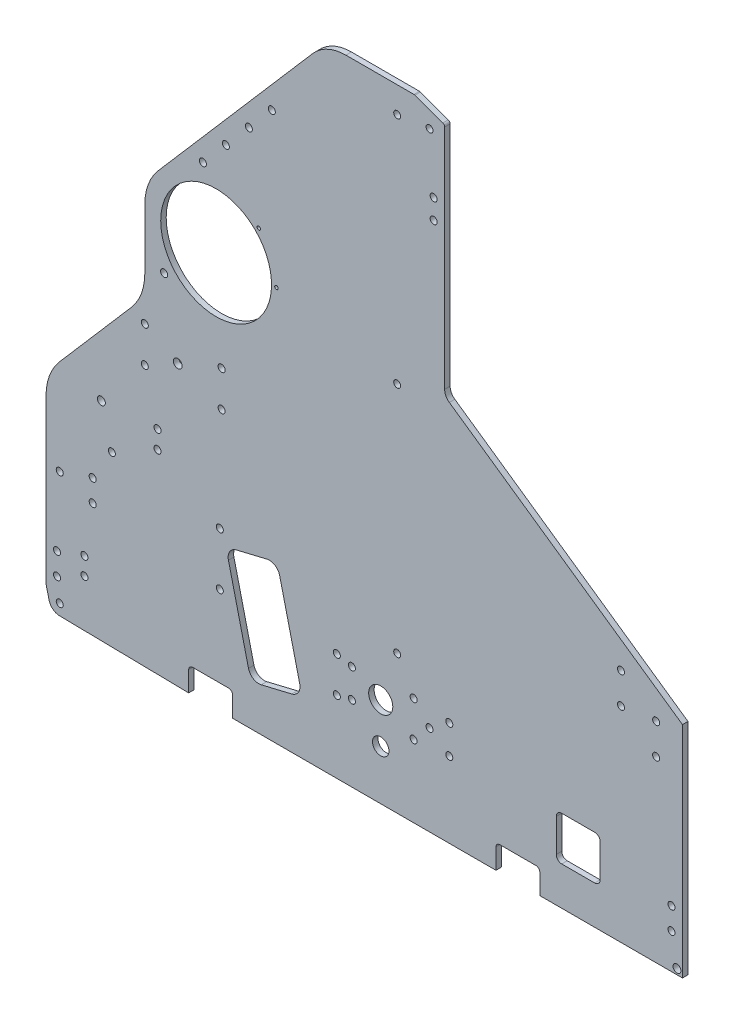
SolidWorks part; units mm, degrees
ref_plane "Front Plane" through (0, 0, 0) normal (0, 0, 1) x (1, 0, 0)
ref_plane "Top Plane" through (0, 0, 0) normal (0, 1, 0) x (1, 0, 0)
ref_plane "Right Plane" through (0, 0, 0) normal (1, 0, 0) x (0, 0, -1)
sketch "Sketch1" plane through (0, 0, 0) normal (0, 0, 1) x (1, 0, 0)
  line L0 (82.55, -20.32) -> (82.55, -6.35)
  line L2 (0, 0) -> (0, 157.48)
  line L4 (368.3, -20.32) -> (368.3, 106.68)
  line L5 (82.55, -6.35) -> (107.95, -6.35)
  line L6 (107.95, -6.35) -> (107.95, -20.32)
  line L7 (107.95, -20.32) -> (260.35, -20.32)
  line L8 (260.35, -20.32) -> (260.35, -6.35)
  line L9 (260.35, -6.35) -> (285.75, -6.35)
  line L10 (285.75, -6.35) -> (285.75, -20.32)
  line L11 (285.75, -20.32) -> (368.3, -20.32)
  line L12 (361.95, 12.7) -> (368.3, 12.7) construction
  line L13 (0, 0) -> (6.35, 0) construction
  line L14 (0.1896, -7.8901) -> (1.7771, -14.2401)
  line L15 (7.8295, -19.0491) -> (82.55, -20.32)
  line L16 (0, 0) -> (0, -6.35)
  line L17 (76.2, 141.605) -> (79.375, 141.605) construction
  line L18 (57.15, 131.2863) -> (101.6, 131.2862) construction
  line L19 (57.15, 131.2863) -> (57.15, 151.9238) construction
  line L20 (101.6, 131.2862) -> (101.6, 151.9237) construction
  line L21 (57.15, 151.9238) -> (101.6, 151.9237) construction
  line L22 (57.15, 131.2863) -> (101.6, 151.9237) construction
  line L23 (101.6, 131.2862) -> (57.15, 151.9238) construction
  line L25 (203.2, 59.805) -> (203.2, 194.805) construction
  line L26 (203.2, 194.805) -> (203.2, 329.805) construction
  line L27 (355.6, 332.105) -> (330.2, 332.105) construction
  line L28 (330.2, 332.105) -> (330.2, 217.805) construction
  line L29 (330.2, 217.805) -> (355.6, 217.805) construction
  line L30 (355.6, 217.805) -> (355.6, 332.105) construction
  line L31 (203.2, 344.805) -> (203.2, 194.805) construction
  line L32 (50.8, 332.105) -> (76.2, 332.105) construction
  line L33 (76.2, 332.105) -> (76.2, 217.805) construction
  line L34 (50.8, 217.805) -> (50.8, 332.105) construction
  line L35 (76.2, 217.805) -> (50.8, 217.805) construction
  line L36 (213.2, 344.805) -> (230.6638, 338.455)
  line L37 (203.2, 344.805) -> (161.925, 344.805)
  line L38 (203.2, 344.805) -> (213.2, 344.805)
  line L39 (348.5362, 344.805) -> (413.4623, 344.805)
  line L40 (348.5362, 344.805) -> (230.6638, 344.805) construction
  line L42 (161.925, 344.805) -> (0, 157.48)
  line L44 (230.6638, 338.455) -> (230.6638, 202.565)
  line L45 (230.6638, 202.565) -> (368.3, 106.68)
  line L46 (213.2, 344.805) -> (-141.0713, 344.805) construction
  circle A0 centre (6.35, 0) radius 2.032
  circle A1 centre (6.35, 12.7) radius 2.032
  circle A2 centre (361.95, 0) radius 2.032
  circle A3 centre (361.95, 12.7) radius 2.032
  arc A5 (1.7771, -14.2401) -> (7.8295, -19.0491) centre (7.9375, -12.7) ccw
  circle A6 centre (7.9375, -12.7) radius 2.032
  arc A7 (0, -6.35) -> (0.1896, -7.8901) centre (6.35, -6.35) ccw
  circle A8 centre (38.1, 78.105) radius 2.032
  circle A9 centre (76.2, 141.605) radius 2.54
  circle A10 centre (101.6, 131.2862) radius 2.032
  circle A11 centre (101.6, 151.9237) radius 2.032
  circle A12 centre (57.15, 151.9238) radius 2.032
  circle A13 centre (57.15, 131.2863) radius 2.032
  circle A15 centre (203.2, 59.805) radius 2
  circle A16 centre (203.2, 194.805) radius 2
  circle A17 centre (203.2, 329.805) radius 2
  circle A18 centre (63.5, 313.055) radius 2.032
  circle A20 centre (355.6, 332.105) radius 2.032
  circle A21 centre (330.2, 332.105) radius 2.032
  circle A22 centre (355.6, 217.805) radius 2.032
  circle A23 centre (330.2, 217.805) radius 2.032
  circle A24 centre (50.8, 332.105) radius 2.032
  circle A25 centre (76.2, 332.105) radius 2.032
  circle A26 centre (50.8, 217.805) radius 2.032
  circle A27 centre (76.2, 217.805) radius 2.032
  circle A28 centre (221.9319, 332.105) radius 2
  circle A29 centre (224.3138, 298.831) radius 2.032
  circle A30 centre (353.06, 100.7351) radius 2.032
  circle A31 centre (332.74, 115.9751) radius 2.032
  circle A32 centre (332.74, 98.1951) radius 2.032
  circle A33 centre (353.06, 82.9551) radius 2.032
  circle A34 centre (117.3562, 280.4276) radius 2.032
  circle A35 centre (104.0678, 265.0548) radius 2.032
  circle A36 centre (90.7795, 249.682) radius 2.032
  circle A38 centre (130.6445, 295.8004) radius 2.032
  circle A39 centre (68.326, 182.9237) radius 2.032
  circle A40 centre (224.3138, 287.401) radius 2.032
  point P82 (203.2, 344.805)
  point P83 (221.9319, 341.63)
  point P90 (368.3, 62.484)
  dimension "D6" = 4.064
  dimension "D10" = 6.35
  dimension "D11" = 4.064
  dimension "D17" = 38.1
  dimension "D27" = 4
  dimension "D31" = 4.064
  dimension "D32" = 41.275
  dimension "D36" = 4.064
  dimension "D47" = 39.624
  dimension "D48" = 4.064
  dimension "D25" = 5.08
  dimension "D26" = 4.064
  dimension "D52" = 4.064
  dimension "D65" = 4.064
  dimension "D2" = 127
  dimension "D3" = 13.97
  dimension "D4" = 25.4
  dimension "D5" = 152.4
  dimension "D7" = 12.7
  dimension "D8" = 6.35
  dimension "D9" = 20.32
  dimension "D12" = 12.7
  dimension "D13" = 1.5875
  dimension "D14" = 82.55
  dimension "D15" = 368.3
  dimension "D16" = 6.35
  dimension "D18" = 98.425
  dimension "D19" = 38.1
  dimension "D20" = 63.5
  dimension "D21" = 3.175
  dimension "D22" = 270
  dimension "D23" = 20.6375
  dimension "D24" = 44.45
  dimension "D28" = 135
  dimension "D29" = 12.7
  dimension "D30" = 15
  dimension "D33" = 63.5
  dimension "D34" = 27.4638
  dimension "D35" = 12.7
  dimension "D37" = 114.3
  dimension "D38" = 25.4
  dimension "D39" = 12.7
  dimension "D40" = 157.48
  dimension "D41" = 142.24
  dimension "D42" = 365.125
  dimension "D43" = 10
  dimension "D44" = 6.35
  dimension "D45" = 31.75
  dimension "D46" = 6.35
  dimension "D49" = 6.35
  dimension "D50" = 203.2
  dimension "D51" = 15.24
  dimension "D53" = 17.78
  dimension "D54" = 17.78
  dimension "D55" = 20.32
  dimension "D56" = 15.24
  dimension "D57" = 92.202
  dimension "D58" = 8.382
  dimension "D59" = 20.32
  dimension "D60" = 20.32
  dimension "D61" = 8.382
  dimension "D62" = 20.32
  dimension "D63" = 8.382
  dimension "D64" = 8.382
  dimension "D66" = 35.052
  dimension "D67" = 68.326
  dimension "D68" = 11.43
extrude "Boss-Extrude1" add sketch "Sketch1" along normal blind 3.175 contours L16 A7 L14 A5 L15 L2 A0 A1 A6 region at (171.3489, 119.5243, 0)
fillet "Fillet1" radius 2.286 4 edges at (285.75, -6.35, 1.5875) (107.95, -6.35, 1.5875) (260.35, -6.35, 1.5875) (82.55, -6.35, 1.5875)
fillet "Fillet2" radius 6.35 1 edges at (230.6638, 202.565, 1.5875)
sketch "Sketch2" plane through (0, 0, 0) normal (0, 0, -1) x (-1, 0, 0)
  circle A0 centre (-100.5528, 71.086) radius 2.032 construction
  circle A1 centre (-100.5528, 40.606) radius 2.032 construction
  circle A2 centre (-22.225, 18.2025) radius 2.032 construction
  circle A3 centre (-22.225, 8.0425) radius 2.032 construction
  circle A4 centre (-100.5528, 71.086) radius 2.032
  circle A5 centre (-100.5528, 40.606) radius 2.032
  circle A6 centre (-22.225, 18.2025) radius 2.032
  circle A7 centre (-22.225, 8.0425) radius 2.032
extrude "Cut-Extrude1" cut sketch "Sketch2" against normal through all
fillet "Fillet3" radius 1.5875 2 edges at (230.6638, 338.455, 1.5875) (213.2, 344.805, 1.5875)
sketch "Sketch3" plane through (0, 0, 3.175) normal (0, 0, 1) x (1, 0, 0)
  line L0 (132.9524, 63.2646) -> (132.7215, 64.2281) construction
  line L1 (128.3814, 66.8897) -> (110.6828, 62.6472) construction
  line L2 (114.5132, 58.4237) -> (126.8822, 61.3887) construction
  line L3 (108.0212, 58.3071) -> (108.2522, 57.3436) construction
  line L4 (131.2006, 57.703) -> (140.0164, 20.9265) construction
  line L5 (144.0993, 16.7636) -> (132.9524, 63.2646) construction
  line L6 (108.2522, 57.3436) -> (119.3991, 10.8426) construction
  line L7 (121.1509, 16.4042) -> (112.3351, 53.1807) construction
  line L8 (119.3991, 10.8426) -> (119.6301, 9.8791) construction
  line L9 (144.3303, 15.8001) -> (144.0993, 16.7636) construction
  line L10 (137.8383, 15.6835) -> (125.4694, 12.7185) construction
  line L11 (123.9701, 7.2175) -> (141.6687, 11.4601) construction
  line L12 (132.9524, 63.2646) -> (132.7215, 64.2281)
  line L13 (128.3814, 66.8897) -> (110.6828, 62.6472)
  line L14 (114.5132, 58.4237) -> (126.8822, 61.3887)
  line L15 (108.0212, 58.3071) -> (108.2522, 57.3436)
  line L16 (131.2006, 57.703) -> (140.0164, 20.9265)
  line L17 (144.0993, 16.7636) -> (132.9524, 63.2646)
  line L18 (108.2522, 57.3436) -> (119.3991, 10.8426)
  line L19 (121.1509, 16.4042) -> (112.3351, 53.1807)
  line L20 (119.3991, 10.8426) -> (119.6301, 9.8791)
  line L21 (144.3303, 15.8001) -> (144.0993, 16.7636)
  line L22 (137.8383, 15.6835) -> (125.4694, 12.7185)
  line L23 (123.9701, 7.2175) -> (141.6687, 11.4601)
  line L24 (127.7894, 69.3598) -> (110.0908, 65.1172)
  line L25 (105.5512, 57.715) -> (105.7822, 56.7515)
  line L26 (105.7822, 56.7515) -> (116.9291, 10.2505)
  line L27 (116.9291, 10.2505) -> (117.16, 9.287)
  line L28 (124.5622, 4.7475) -> (142.2608, 8.99)
  line L29 (146.8003, 16.3922) -> (146.5694, 17.3557)
  line L30 (146.5694, 17.3557) -> (135.4225, 63.8567)
  line L31 (135.4225, 63.8567) -> (135.1915, 64.8202)
  line L32 (14.605, -0.1369) -> (103.7278, 32.3011) construction
  line L33 (14.605, -0.1369) -> (103.7278, 32.3011)
  line L35 (-39.6666, 74.7152) -> (103.7278, 126.9065) construction
  arc A0 (132.7215, 64.2281) -> (128.6308, 66.9403) centre (129.2206, 63.3889) ccw construction
  arc A1 (110.6828, 62.6472) -> (110.4377, 62.5791) centre (111.522, 59.1463) ccw construction
  arc A2 (128.6308, 66.9403) -> (128.3814, 66.8897) centre (129.2206, 63.3889) ccw construction
  arc A3 (110.4377, 62.5791) -> (108.0212, 58.3071) centre (111.522, 59.1463) ccw construction
  arc A4 (119.6301, 9.8791) -> (123.7207, 7.1669) centre (123.1309, 10.7183) ccw construction
  arc A5 (141.9139, 11.5281) -> (144.3303, 15.8001) centre (140.8295, 14.9609) ccw construction
  arc A6 (141.6687, 11.4601) -> (141.9139, 11.5281) centre (140.8295, 14.9609) ccw construction
  arc A7 (123.7207, 7.1669) -> (123.9701, 7.2175) centre (123.1309, 10.7183) ccw construction
  arc A8 (132.7215, 64.2281) -> (128.6308, 66.9403) centre (129.2206, 63.3889) ccw
  arc A9 (110.6828, 62.6472) -> (110.4377, 62.5791) centre (111.522, 59.1463) ccw
  arc A10 (128.6308, 66.9403) -> (128.3814, 66.8897) centre (129.2206, 63.3889) ccw
  arc A11 (110.4377, 62.5791) -> (108.0212, 58.3071) centre (111.522, 59.1463) ccw
  arc A12 (119.6301, 9.8791) -> (123.7207, 7.1669) centre (123.1309, 10.7183) ccw
  arc A13 (141.9139, 11.5281) -> (144.3303, 15.8001) centre (140.8295, 14.9609) ccw
  arc A14 (141.6687, 11.4601) -> (141.9139, 11.5281) centre (140.8295, 14.9609) ccw
  arc A15 (123.7207, 7.1669) -> (123.9701, 7.2175) centre (123.1309, 10.7183) ccw
  arc A16 (110.0908, 65.1172) -> (109.6726, 65.0012) centre (111.522, 59.1463) ccw
  arc A17 (109.6726, 65.0012) -> (105.5512, 57.715) centre (111.522, 59.1463) ccw
  arc A18 (117.16, 9.287) -> (124.1369, 4.6613) centre (123.1309, 10.7183) ccw
  arc A19 (124.1369, 4.6613) -> (124.5622, 4.7475) centre (123.1309, 10.7183) ccw
  arc A20 (142.2608, 8.99) -> (142.6789, 9.1061) centre (140.8295, 14.9609) ccw
  arc A21 (142.6789, 9.1061) -> (146.8003, 16.3922) centre (140.8295, 14.9609) ccw
  arc A22 (135.1915, 64.8202) -> (128.2147, 69.446) centre (129.2206, 63.3889) ccw
  arc A23 (128.2147, 69.446) -> (127.7894, 69.3598) centre (129.2206, 63.3889) ccw
  circle A24 centre (64.5259, 102.9405) radius 2.032 construction
  circle A25 centre (64.5259, 92.5258) radius 2.032 construction
  circle A26 centre (133.35, 208.2281) radius 1.016 construction
  circle A33 centre (26.9875, 46.9531) radius 2.032
  circle A34 centre (26.9875, 59.6531) radius 2.032
  circle A35 centre (7.9375, 53.3031) radius 2.032
  circle A36 centre (7.9375, 53.3031) radius 2.032 construction
  circle A37 centre (32.0306, 100.8109) radius 31.75 construction
  circle A38 centre (32.0306, 100.8109) radius 2.286
  circle A39 centre (123.1207, 232.9238) radius 1.016 construction
  circle A40 centre (64.5259, 102.9405) radius 2.032
  circle A41 centre (64.5259, 92.5258) radius 2.032
  circle A42 centre (133.35, 208.2281) radius 1.016
  circle A43 centre (123.1207, 232.9238) radius 1.016
  circle A44 centre (26.9875, 59.6531) radius 2.032 construction
  circle A45 centre (26.9875, 46.9531) radius 2.032 construction
  ellipse E0 centre (124.5974, 48.8487) end of major axis (128.5376, 61.3578) minor radius 6 (131.2006, 57.703) -> (126.8822, 61.3887) ccw construction
  ellipse E1 centre (122.2349, 48.2824) end of major axis (113.0518, 57.6456) minor radius 6 (114.5132, 58.4237) -> (112.3351, 53.1807) ccw construction
  ellipse E2 centre (127.7541, 25.2585) end of major axis (131.6942, 37.7675) minor radius 6 (121.1509, 16.4042) -> (125.4694, 12.7185) ccw construction
  ellipse E3 centre (130.1166, 25.8248) end of major axis (139.2998, 16.4616) minor radius 6 (137.8383, 15.6835) -> (140.0164, 20.9265) ccw construction
  ellipse E4 centre (124.5974, 48.8487) end of major axis (128.5376, 61.3578) minor radius 6 (131.2006, 57.703) -> (126.8822, 61.3887) ccw
  ellipse E5 centre (122.2349, 48.2824) end of major axis (131.4181, 38.9192) minor radius 6 (114.5132, 58.4237) -> (112.3351, 53.1807) ccw
  ellipse E6 centre (127.7541, 25.2585) end of major axis (123.8139, 12.7495) minor radius 6 (121.1509, 16.4042) -> (125.4694, 12.7185) ccw
  ellipse E7 centre (130.1166, 25.8248) end of major axis (139.2998, 16.4616) minor radius 6 (137.8383, 15.6835) -> (140.0164, 20.9265) ccw
  point P115 (32.0306, 100.8109)
  dimension "D3" = 63.5
  dimension "D4" = 4.572
  dimension "D2" = 88.9
  dimension "D1" = 2.54
extrude "Cut-Extrude2" cut sketch "Sketch3" against normal through all contours A22 A23 L24 A16 A17 L25 L26 L27 A18 A19 L28 A20 A21 L29 L30 L31 A15 A12 L20 L18 L15 A11 A9 L13 A10 A8 L12 L17 L21 A13 A14 L23 | A12 A15 L23 A14 A13 L21 L17 L12 A8 A10 L13 A9 A11 L15 L18 L20 E7 L22 E6 L19 E5 L14 E4 L16 | L22 E7 L16 E4 L14 E5 L19 E6 | A38 | A41 | A40 | A35 | A34 | A33 | A43 | A42 region at (137.844, 39.8506, 3.175) region at (126.1758, 37.0536, 3.175) region at (128.1544, 68.6507, 3.175) region at (32.0306, 100.8109, 3.175) region at (64.5259, 102.9405, 3.175) region at (64.5259, 92.5258, 3.175)
sketch "Sketch4" plane through (0, 0, 3.175) normal (0, 0, 1) x (1, 0, 0)
  line L0 (57.15, 151.9238) -> (101.6, 151.9237) construction
  line L1 (168.275, 21.4312) -> (212.725, 21.4312) construction
  line L2 (168.275, 21.4312) -> (168.275, 42.0687) construction
  line L3 (168.275, 42.0687) -> (212.725, 42.0687) construction
  line L4 (212.725, 21.4312) -> (212.725, 42.0687) construction
  line L5 (168.275, 21.4312) -> (212.725, 42.0687) construction
  line L6 (168.275, 42.0687) -> (212.725, 21.4312) construction
  line L7 (57.15, 131.2863) -> (57.15, 151.9238) construction
  line L8 (107.95, -20.32) -> (260.35, -20.32) construction
  line L9 (193.675, 31.75) -> (177.005, 31.75) construction
  line L10 (190.5, 31.75) -> (193.675, 31.75) construction
  line L11 (6.35, 12.7) -> (361.95, 12.7) construction
  line L12 (107.95, -6.35) -> (107.95, -20.32) construction
  line L13 (193.675, 31.75) -> (220.6625, 31.75) construction
  line L14 (177.005, 23.4569) -> (177.005, 40.0431) construction
  line L15 (213.2, 44.805) -> (193.2, 44.805) construction
  line L16 (213.2, 44.805) -> (213.2, 344.805) construction
  line L17 (213.2, 344.805) -> (193.2, 344.805) construction
  line L18 (193.2, 44.805) -> (193.2, 344.805) construction
  line L19 (213.2, 44.805) -> (193.2, 344.805) construction
  line L20 (213.2, 344.805) -> (193.2, 44.805) construction
  line L21 (226.9319, 332.105) -> (226.9319, 31.75) construction
  line L22 (237.33, 40.0431) -> (233.3612, 40.0431) construction
  line L23 (237.33, 23.4569) -> (233.3612, 23.4569) construction
  circle A0 centre (168.275, 42.0687) radius 2.032
  circle A1 centre (212.725, 42.0687) radius 2.032
  circle A2 centre (212.725, 21.4312) radius 2.032
  circle A3 centre (168.275, 21.4312) radius 2.032
  circle A4 centre (193.675, 31.75) radius 6.985
  circle A7 centre (220.6625, 31.75) radius 14.2875 construction
  circle A8 centre (193.675, 31.75) radius 12.7 construction
  circle A9 centre (177.005, 40.0431) radius 2.032
  circle A10 centre (177.005, 23.4569) radius 2.032
  circle A11 centre (237.33, 40.0431) radius 2.032 construction
  circle A12 centre (237.33, 23.4569) radius 2.032 construction
  circle A13 centre (193.675, 8.4667) radius 4.7625
  circle A14 centre (221.9319, 31.75) radius 2.032
  circle A15 centre (221.9319, 31.75) radius 5 construction
  circle A16 centre (221.9319, 332.105) radius 5 construction
  circle A17 centre (233.3612, 23.4569) radius 2.032
  circle A18 centre (233.3612, 40.0431) radius 2.032
  point P0 (190.5, 31.75)
  point P26 (203.2, 194.805)
  point P38 (177.005, 31.75)
  dimension "D1" = 4.064
  dimension "D4" = 13.97
  dimension "D7" = 9.525
  dimension "D10" = 25.4
  dimension "D11" = 28.575
  dimension "D16" = 10
  dimension "D17" = 4.064
  dimension "D18" = 10
  dimension "D2" = 52.07
  dimension "D3" = 3.175
  dimension "D5" = 82.55
  dimension "D6" = 26.9875
  dimension "D8" = 20
  dimension "D9" = 300
  dimension "D12" = 16.67
  dimension "D13" = 16.5862
  dimension "D14" = 60.325
  dimension "D15" = 23.2833
  dimension "D19" = 3.9688
extrude "Cut-Extrude3" cut sketch "Sketch4" against normal through all
sketch "Sketch5" plane through (0, 0, -187.325) normal (0, 0, -1) x (-1, 0, 0)
  line L0 (-57.15, 223.5947) -> (-57.15, 165.3337)
  line L1 (-161.925, 344.805) -> (-52.7201, 218.4699) construction
  line L2 (-57.15, 165.3337) -> (0, 99.219)
  line L3 (0, -6.35) -> (0, 157.48) construction
  line L4 (-50.4199, 215.8089) -> (0, 157.48) construction
  line L5 (-50.4199, 215.8089) -> (0, 157.48) construction
  line L6 (-57.15, 223.5947) -> (0, 157.48)
  line L7 (0, 157.48) -> (0, 99.219)
  circle A0 centre (-98.425, 208.2281) radius 32.0675
  circle A1 centre (-365.125, -17.145) radius 2.286 construction
  circle A2 centre (-365.125, -17.145) radius 2.286
  dimension "D3" = 64.135
  dimension "D1" = 38.1
  dimension "D2" = 57.15
  dimension "D4" = 41.275
  dimension "D5" = 41.275
extrude "Cut-Extrude5" cut sketch "Sketch5" against normal through all contours A0 | L7 L6 L0 L2 | A2 region at (28.575, 161.4068, -187.325) region at (98.425, 208.2281, -187.325)
fillet "Fillet4" radius 31.75 3 edges at (0, 99.219, 1.5875) (57.15, 165.3337, 1.5875) (57.15, 223.5947, 1.5875)
sketch "Sketch6" plane through (0, 0, 3.175) normal (0, 0, 1) x (1, 0, 0)
  line L0 (285.75, -20.32) -> (368.3, -20.32) construction
  line L1 (298.45, 27.305) -> (317.5, 27.305)
  line L2 (295.275, 24.13) -> (295.275, 5.08)
  line L3 (298.45, 1.905) -> (317.5, 1.905)
  line L4 (320.675, 24.13) -> (320.675, 5.08)
  line L5 (295.275, 27.305) -> (320.675, 1.905) construction
  line L6 (295.275, 1.905) -> (320.675, 27.305) construction
  line L7 (368.3, -20.32) -> (368.3, 106.68) construction
  arc A0 (295.275, 5.08) -> (298.45, 1.905) centre (298.45, 5.08) ccw
  arc A1 (317.5, 1.905) -> (320.675, 5.08) centre (317.5, 5.08) ccw
  arc A2 (317.5, 27.305) -> (320.675, 24.13) centre (317.5, 24.13) cw
  arc A3 (298.45, 27.305) -> (295.275, 24.13) centre (298.45, 24.13) ccw
  point P0 (307.975, 14.605)
  dimension "D2" = 3.175
  dimension "D1" = 25.4
  dimension "D3" = 22.225
  dimension "D4" = 47.625
extrude "Cut-Extrude6" cut sketch "Sketch6" against normal through all
sketch "Sketch7" plane through (0, 0, 0) normal (0, 0, -1) x (-1, 0, 0)
  circle A0 centre (-215.9, 306.705) radius 2.032 construction
  arc A1 (-201.2648, 307.3246) -> (-201.2648, 306.0854) centre (-203.2, 306.705) ccw construction
  arc A2 (-192.4352, 306.0854) -> (-192.4352, 307.3246) centre (-190.5, 306.705) ccw construction
  arc A3 (-176.9699, 308.5597) -> (-176.9699, 304.8503) centre (-177.8, 306.705) ccw construction
  circle A4 centre (-215.9, 255.905) radius 2.032 construction
  arc A5 (-201.2648, 256.5246) -> (-201.2648, 255.2854) centre (-203.2, 255.905) ccw construction
  arc A6 (-192.4352, 255.2854) -> (-192.4352, 256.5246) centre (-190.5, 255.905) ccw construction
  arc A7 (-176.9699, 257.7597) -> (-176.9699, 254.0503) centre (-177.8, 255.905) ccw construction
  circle A8 centre (-215.9, 306.705) radius 2.032
  arc A9 (-201.2648, 307.3246) -> (-201.2648, 306.0854) centre (-203.2, 306.705) ccw
  arc A10 (-192.4352, 306.0854) -> (-192.4352, 307.3246) centre (-190.5, 306.705) ccw
  arc A11 (-176.9699, 308.5597) -> (-176.9699, 304.8503) centre (-177.8, 306.705) ccw
  circle A12 centre (-215.9, 255.905) radius 2.032
  arc A13 (-201.2648, 256.5246) -> (-201.2648, 255.2854) centre (-203.2, 255.905) ccw
  arc A14 (-192.4352, 255.2854) -> (-192.4352, 256.5246) centre (-190.5, 255.905) ccw
  arc A15 (-176.9699, 257.7597) -> (-176.9699, 254.0503) centre (-177.8, 255.905) ccw
  circle A16 centre (-203.2, 306.705) radius 2.032
  circle A17 centre (-190.5, 306.705) radius 2.032
  circle A18 centre (-177.8, 306.705) radius 2.032
  circle A19 centre (-177.8, 255.905) radius 2.032
  circle A20 centre (-190.5, 255.905) radius 2.032
  circle A21 centre (-203.2, 255.905) radius 2.032
  dimension "D1" = 4.064
extrude "Cut-Extrude7" cut sketch "Sketch7" against normal blind 2.54 contours A12 | A13 A21 | A14 A20 | A15 A19 | A8 | A9 A16 | A10 A17 | A11 A18 region at (215.9, 306.705, 0) region at (203.2, 306.705, 0) region at (190.5, 306.705, 0) region at (177.8, 306.705, 0) region at (215.9, 255.905, 0) region at (203.2, 255.905, 0) region at (190.5, 255.905, 0) region at (177.8, 255.905, 0)
fillet "Fillet5" radius 25.4 1 edges at (161.925, 344.805, 1.5875)
